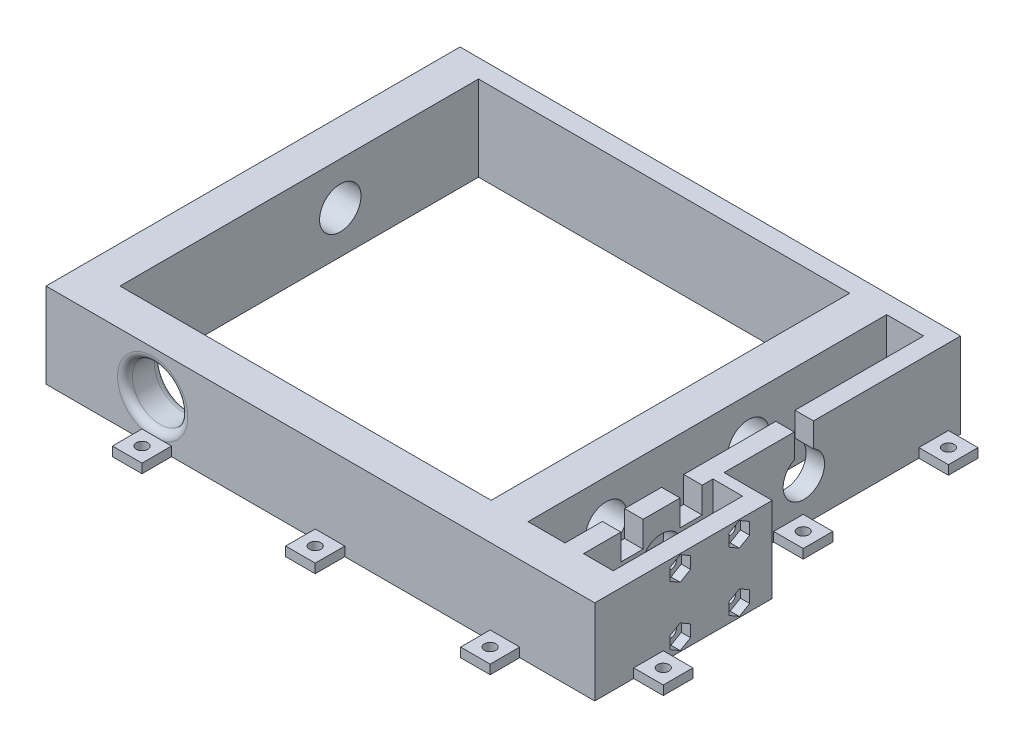
SolidWorks part; units mm, degrees
ref_plane "Front Plane" through (0, 0, 0) normal (0, 0, 1) x (1, 0, 0)
ref_plane "Top Plane" through (0, 0, 0) normal (0, 1, 0) x (1, 0, 0)
ref_plane "Right Plane" through (0, 0, 0) normal (1, 0, 0) x (0, 0, -1)
sketch "Sketch1" plane through (0, 0, 0) normal (0, 1, 0) x (1, 0, 0)
  line L0 (-50, -27.5) -> (-50, 27.5) construction
  line L1 (-40, -17.5) -> (40, -17.5) construction
  line L2 (-40, -17.5) -> (-40, 17.5) construction
  line L3 (-40, 17.5) -> (40, 17.5) construction
  line L4 (40, -17.5) -> (40, 17.5) construction
  line L5 (-40, -17.5) -> (40, 17.5) construction
  line L6 (-40, 17.5) -> (40, -17.5) construction
  line L7 (-50, 27.5) -> (50, 27.5) construction
  line L8 (50, -27.5) -> (50, 27.5) construction
  line L9 (-50, -27.5) -> (50, -27.5) construction
  line L10 (50, 0) -> (50.2, 0) construction
  line L11 (-50, 0) -> (-50.2, 0) construction
  line L12 (50.2, 0) -> (50.2, -27.5)
  line L13 (50.2, -27.5) -> (50.2, -47.5)
  line L14 (-50.2, 0) -> (-50.2, -27.5)
  line L15 (-50.2, -27.5) -> (-50.2, -47.5)
  line L16 (-50.2, -47.5) -> (50.2, -47.5)
  line L17 (50.2, 0) -> (50.2, 54.5)
  line L18 (-50.2, 0) -> (-50.2, 54.5)
  line L19 (-60.2, 0) -> (-60.2, 54.5)
  line L20 (-60.2, 0) -> (-60.2, -27.5)
  line L21 (-60.2, -27.5) -> (-60.2, -57.5)
  line L22 (-60.2, -57.5) -> (60.2, -57.5)
  line L23 (60.2, -27.5) -> (60.2, -57.5) construction
  line L24 (60.2, 0) -> (60.2, -27.5)
  line L25 (60.2, 0) -> (60.2, 54.5)
  line L26 (-50.2, 54.5) -> (-60.2, 54.5)
  line L27 (50.2, 54.5) -> (60.2, 54.5)
  line L28 (83.24, -47.5) -> (83.24, -9.5)
  line L29 (60.2, -57.5) -> (83.24, -57.5)
  line L31 (60.2, -47.5) -> (83.24, -47.5)
  line L32 (83.24, -57.5) -> (83.24, -47.5) construction
  line L33 (83.24, -57.5) -> (88.24, -57.5)
  line L34 (83.24, -57.5) -> (83.24, -9.5) construction
  line L35 (83.24, -9.5) -> (88.24, -9.5)
  line L36 (88.24, -57.5) -> (88.24, -9.5)
  line L37 (60.2, -47.5) -> (60.2, 54.5)
  line L39 (70.2, -47.5) -> (75.2, -47.5)
  line L40 (70.2, -47.5) -> (70.2, -9.5)
  line L41 (70.2, -9.5) -> (75.2, -9.5) construction
  line L42 (75.2, -47.5) -> (75.2, -9.5)
  line L43 (75.2, -9.5) -> (83.24, -9.5)
  line L44 (75.2, -9.5) -> (75.2, -12.5)
  line L45 (75.2, -12.5) -> (83.24, -12.5)
  line L46 (83.24, -9.5) -> (83.24, -12.5)
  line L47 (70.2, -9.5) -> (75.2, -9.5) construction
  line L48 (70.2, -9.5) -> (70.2, 54.5)
  line L49 (70.2, 54.5) -> (75.2, 54.5)
  line L50 (75.2, -9.5) -> (75.2, 54.5)
  line L51 (-50.2, 54.5) -> (50.2, 54.5)
  line L52 (-50.2, 54.5) -> (-50.2, 49.5)
  line L53 (-50.2, 49.5) -> (50.2, 49.5)
  line L54 (50.2, 54.5) -> (50.2, 49.5)
  line L55 (60.2, 54.5) -> (70.2, 54.5)
  line L56 (60.2, 54.5) -> (60.2, 49.5)
  line L57 (60.2, 49.5) -> (70.2, 49.5)
  line L58 (70.2, 54.5) -> (70.2, 49.5)
  point P0 (0, 0)
  point P10 (50, 0)
  point P11 (0, -27.5)
  point P12 (0, 27.5)
  point P13 (-50, 0)
  dimension "D1" = 80
  dimension "D2" = 35
  dimension "D4" = 0.2
  dimension "D5" = 20
  dimension "D7" = 8.04
  dimension "D8" = 5
  dimension "D9" = 10
  dimension "D10" = 5
  dimension "D11" = 38
  dimension "D12" = 3
  dimension "D13" = 22
  dimension "D14" = 5
  dimension "D3" = 10
  dimension "D6" = 10
extrude "Boss-Extrude1" add sketch "Sketch1" along normal mid plane 23 contours L31 L37 L24 L25 L27 L17 L12 L13 L16 L15 L14 L18 L26 L19 L20 L21 L22 L29 L33 L36 L35 L28 | L31 L42 L41 L40 | L42 L45 L28 L43 | L18 L53 L17 L51 | L37 L57 L48 L55 region at (52.0595, 0, -24.75) region at (0, 0, -52) region at (65.2, 0, -52) region at (72.7, 0, -3.5) region at (79.22, 0, 11)
sketch "Sketch2" plane through (60.2, 0, 0) normal (1, 0, 0) x (0, 0, -1)
  line L4 (-47.5, -11.5) -> (49.5, -11.5)
  line L5 (49.5, -11.5) -> (49.5, 11.5)
  line L6 (-47.5, -11.5) -> (49.5, -11.5)
  line L7 (49.5, 11.5) -> (-47.5, 11.5)
  line L12 (49.5, -11.5) -> (49.5, 11.5)
  line L14 (49.5, 11.5) -> (-47.5, 11.5)
  line L15 (-47.5, 11.5) -> (-47.5, -11.5)
  line L16 (-47.5, 11.5) -> (-47.5, -11.5)
  circle A0 centre (12.106, 0) radius 5.6
  circle A1 centre (12.106, 0) radius 34.1 construction
  circle A4 centre (-26.394, 0) radius 5.6
  circle A5 centre (-26.394, 0) radius 4.4 construction
  dimension "D2" = 11.2
  dimension "D3" = 68.2
  dimension "D5" = 8.8
  dimension "D4" = 38.5
  dimension "D1" = 0
extrude "Cut-Extrude1" cut sketch "Sketch2" against normal up to surface (120.4 mm away) contours A0 up to face at (-60.2, 0, 1.5)
sketch "Sketch3" plane through (60.2, 0, 0) normal (1, 0, 0) x (0, 0, -1)
  circle A0 centre (-26.394, 0) radius 5.6 construction
  circle A1 centre (-26.394, 0) radius 5.6
extrude "Cut-Extrude2" cut sketch "Sketch3" against normal up to next
sketch "Sketch8" plane through (70.2, 0, 0) normal (-1, 0, 0) x (0, 0, 1)
  circle A0 centre (26.394, 0) radius 5.6 construction
  circle A1 centre (26.394, 0) radius 5.6
extrude "Cut-Extrude5" cut sketch "Sketch8" against normal up to surface (5 mm away) up to face at (75.2, 0, 30)
sketch "Sketch10" plane through (83.24, 0, 0) normal (-1, 0, 0) x (0, 0, 1)
  line L1 (18.394, -8) -> (34.394, -8) construction
  line L2 (18.394, -8) -> (18.394, 8) construction
  line L3 (18.394, 8) -> (34.394, 8) construction
  line L4 (34.394, -8) -> (34.394, 8) construction
  line L5 (18.394, -8) -> (34.394, 8) construction
  line L6 (18.394, 8) -> (34.394, -8) construction
  circle A0 centre (26.394, 0) radius 5.6 construction
  circle A1 centre (26.394, 0) radius 5.6 construction
  circle A2 centre (18.394, 8) radius 1.8
  circle A3 centre (34.394, -8) radius 1.8
  circle A4 centre (18.394, -8) radius 1.8
  circle A5 centre (34.394, 8) radius 1.8
  dimension "D2" = 3.6
  dimension "D1" = 16
extrude "Boss-Extrude4" add sketch "Sketch10" along normal blind 1
sketch "Sketch11" plane through (82.24, 0, 0) normal (-1, 0, 0) x (0, 0, 1)
  circle A0 centre (18.394, 8) radius 1.5
  circle A1 centre (34.394, 8) radius 1.5
  circle A2 centre (34.394, -8) radius 1.5
  circle A3 centre (18.394, -8) radius 1.5
  dimension "D1" = 3
extrude "Cut-Extrude6" cut sketch "Sketch11" against normal up to surface (6 mm away) up to face at (88.24, 0, 33.5)
sketch "Sketch12" plane through (88.24, 0, 0) normal (1, 0, 0) x (0, 0, -1)
  line L1 (-31.594, 9.6166) -> (-34.394, 11.2332)
  line L2 (-34.394, 11.2332) -> (-37.194, 9.6166)
  line L3 (-37.194, 9.6166) -> (-37.194, 6.3834)
  line L4 (-57.5, -11.5) -> (-9.5, -11.5)
  line L5 (-9.5, -11.5) -> (-9.5, 11.5)
  line L6 (-9.5, 11.5) -> (-57.5, 11.5)
  line L7 (-57.5, 11.5) -> (-57.5, -11.5)
  line L8 (-57.5, -11.5) -> (-9.5, -11.5)
  line L10 (-9.5, 11.5) -> (-57.5, 11.5)
  line L12 (-37.194, 6.3834) -> (-34.394, 4.7668)
  line L13 (-34.394, 4.7668) -> (-31.594, 6.3834)
  line L14 (-31.594, 6.3834) -> (-31.594, 9.6166)
  line L15 (-18.394, 11.2332) -> (-21.194, 9.6166)
  line L16 (-21.194, 9.6166) -> (-21.194, 6.3834)
  line L17 (-21.194, 6.3834) -> (-18.394, 4.7668)
  line L18 (-18.394, 4.7668) -> (-15.594, 6.3834)
  line L19 (-15.594, 6.3834) -> (-15.594, 9.6166)
  line L20 (-15.594, 9.6166) -> (-18.394, 11.2332)
  line L21 (-31.594, -6.3834) -> (-34.394, -4.7668)
  line L22 (-34.394, -4.7668) -> (-37.194, -6.3834)
  line L23 (-37.194, -6.3834) -> (-37.194, -9.6166)
  line L24 (-37.194, -9.6166) -> (-34.394, -11.2332)
  line L25 (-34.394, -11.2332) -> (-31.594, -9.6166)
  line L26 (-31.594, -9.6166) -> (-31.594, -6.3834)
  line L27 (-15.594, -6.3834) -> (-18.394, -4.7668)
  line L28 (-18.394, -4.7668) -> (-21.194, -6.3834)
  line L29 (-21.194, -6.3834) -> (-21.194, -9.6166)
  line L30 (-21.194, -9.6166) -> (-18.394, -11.2332)
  line L31 (-18.394, -11.2332) -> (-15.594, -9.6166)
  line L32 (-15.594, -9.6166) -> (-15.594, -6.3834)
  line L36 (-9.5, -11.5) -> (-9.5, 11.5)
  line L38 (-57.5, 11.5) -> (-57.5, -11.5)
  circle A0 centre (-34.394, 8) radius 2.8 construction
  circle A1 centre (-18.394, 8) radius 2.8 construction
  circle A2 centre (-34.394, -8) radius 2.8 construction
  circle A3 centre (-18.394, -8) radius 2.8 construction
  circle M5 centre (-18.394, -8) radius 1.5
  circle M6 centre (-34.394, -8) radius 1.5
  circle M7 centre (-34.394, 8) radius 1.5
  circle M8 centre (-18.394, 8) radius 1.5
  line M11 (-9.5, 11.5) -> (-57.5, 11.5)
  dimension "D2" = 5.6
  dimension "D1" = 0
extrude "Cut-Extrude7" cut sketch "Sketch12" against normal blind 2.5 contours L13 L14 L1 L2 L3 L12 M11 M7 | L19 L20 L10 L15 L16 L17 L18 M8 | L31 L32 L27 L28 L29 L30 L8 M5 | L25 L26 L21 L22 L23 L24 L8 M6 region at (88.24, 8, 31.6795) region at (88.24, 10.3508, 17.0368) region at (88.24, -8, 31.6795) region at (88.24, -8, 15.6795)
sketch "Sketch13" plane through (75.2, 0, 0) normal (1, 0, 0) x (0, 0, -1)
  line L0 (-57.5, 11.5) -> (-9.5, 11.5) construction
  line L1 (-37.394, 4.5) -> (-31.394, 4.5)
  line L2 (-37.394, 4.5) -> (-37.394, 11.5)
  line L3 (-37.394, 11.5) -> (-31.394, 11.5)
  line L4 (-31.394, 4.5) -> (-31.394, 11.5)
  line L5 (-37.394, 4.5) -> (-31.394, 11.5) construction
  line L6 (-37.394, 11.5) -> (-31.394, 4.5) construction
  line L7 (-21.394, 4.5) -> (-15.394, 4.5)
  line L8 (-21.394, 4.5) -> (-21.394, 11.5)
  line L9 (-21.394, 11.5) -> (-15.394, 11.5)
  line L10 (-15.394, 4.5) -> (-15.394, 11.5)
  line L11 (-21.394, 4.5) -> (-15.394, 11.5) construction
  line L12 (-21.394, 11.5) -> (-15.394, 4.5) construction
  line L13 (-21.394, -11.5) -> (-15.394, -11.5)
  line L14 (-21.394, -11.5) -> (-21.394, -4.5)
  line L15 (-21.394, -4.5) -> (-15.394, -4.5)
  line L16 (-15.394, -11.5) -> (-15.394, -4.5)
  line L17 (-21.394, -11.5) -> (-15.394, -4.5) construction
  line L18 (-21.394, -4.5) -> (-15.394, -11.5) construction
  line L19 (-37.394, -11.5) -> (-31.394, -11.5)
  line L20 (-37.394, -11.5) -> (-37.394, -4.5)
  line L21 (-37.394, -4.5) -> (-31.394, -4.5)
  line L22 (-31.394, -11.5) -> (-31.394, -4.5)
  line L23 (-37.394, -11.5) -> (-31.394, -4.5) construction
  line L24 (-37.394, -4.5) -> (-31.394, -11.5) construction
  line L25 (-57.5, -11.5) -> (-9.5, -11.5) construction
  circle A0 centre (-34.394, -8) radius 1.5 construction
  circle A1 centre (-18.394, -8) radius 1.5 construction
  circle A2 centre (-18.394, 8) radius 1.5 construction
  circle A3 centre (-34.394, 8) radius 1.5 construction
  circle A4 centre (-34.394, -8) radius 1.5 construction
  circle A5 centre (-18.394, -8) radius 1.5 construction
  circle A6 centre (-18.394, 8) radius 1.5 construction
  circle A7 centre (-34.394, 8) radius 1.5 construction
  point P23 (-18.394, 8)
  point P28 (-18.394, -8)
  point P33 (-34.394, -8)
  dimension "D1" = 6
extrude "Cut-Extrude9" cut sketch "Sketch13" against normal up to surface (5 mm away) up to face at (70.2, 0, 31.994)
sketch "Sketch14" plane through (70.2, 0, 0) normal (-1, 0, 0) x (0, 0, 1)
  line L0 (15.394, 11.5) -> (-49.5, 11.5) construction
  line L1 (-14.706, 4.9598) -> (-9.506, 4.9598)
  line L2 (-14.706, 4.9598) -> (-14.706, 11.5)
  line L3 (-14.706, 11.5) -> (-9.506, 11.5)
  line L4 (-9.506, 4.9598) -> (-9.506, 11.5)
  circle A0 centre (-12.106, 0) radius 5.6 construction
  circle A1 centre (-12.106, 0) radius 5.6
  line M13 (15.394, 11.5) -> (-49.5, 11.5)
  dimension "D1" = 5.2
extrude "Cut-Extrude10" cut sketch "Sketch14" against normal up to next contours L1 A1 | A1 L4 L2 M13 | L1 A1 region at (70.2, 5.2172, -12.106) region at (70.2, 8.4429, -12.106) region at (70.2, -0.1217, -12.106)
sketch "Sketch15" plane through (0, 0, 57.5) normal (0, 0, 1) x (1, 0, 0)
  line L5 (-60.2, -11.5) -> (88.24, -11.5) construction
  line L6 (-34.3437, -11.5) -> (-28.3437, -11.5)
  circle A0 centre (-31.3437, 0) radius 7.5
  dimension "D3" = 15
extrude "Cut-Extrude11" cut sketch "Sketch15" against normal up to surface (10 mm away) contours A0 region at (-31.3437, 0, 57.5) up to face at (0, 0, 47.5)
fillet "Fillet1" radius 2 2 edges at (-38.8437, 0, 47.5) (-23.8437, 0, 57.5)
sketch "Sketch16" plane through (0, -11.5, 0) normal (0, -1, 0) x (1, 0, 0)
  line L0 (-60.2, 57.5) -> (-60.2, -54.5) construction
  line L1 (-60.2, -54.5) -> (75.2, -54.5) construction
  line L2 (75.2, 9.5) -> (75.2, -54.5) construction
  line L3 (88.24, 57.5) -> (88.24, 9.5) construction
  line L4 (-60.2, 57.5) -> (88.24, 57.5) construction
  line L6 (-26.235, 57.5) -> (-34.235, 57.5)
  line L7 (-26.235, 57.5) -> (-26.235, 65.5)
  line L8 (-26.235, 65.5) -> (-34.235, 65.5)
  line L9 (-34.235, 57.5) -> (-34.235, 65.5)
  line L10 (-60.2, 44.1008) -> (-68.2, 44.1008)
  line L11 (-60.2, 44.1008) -> (-60.2, 36.1008)
  line L12 (-60.2, 36.1008) -> (-68.2, 36.1008)
  line L13 (-68.2, 44.1008) -> (-68.2, 36.1008)
  line L14 (-60.2, -36.5827) -> (-68.2, -36.5827)
  line L15 (-60.2, -36.5827) -> (-60.2, -44.5827)
  line L16 (-60.2, -44.5827) -> (-68.2, -44.5827)
  line L17 (-68.2, -36.5827) -> (-68.2, -44.5827)
  line L18 (-36.4203, -54.5) -> (-28.4203, -54.5)
  line L19 (-36.4203, -54.5) -> (-36.4203, -62.5)
  line L20 (-36.4203, -62.5) -> (-28.4203, -62.5)
  line L21 (-28.4203, -54.5) -> (-28.4203, -62.5)
  line L22 (-5.3881, -54.5) -> (2.6119, -54.5)
  line L23 (-5.3881, -54.5) -> (-5.3881, -62.5)
  line L24 (-5.3881, -62.5) -> (2.6119, -62.5)
  line L25 (2.6119, -54.5) -> (2.6119, -62.5)
  line L26 (46.8273, -54.5) -> (54.8273, -54.5)
  line L27 (46.8273, -54.5) -> (46.8273, -62.5)
  line L28 (46.8273, -62.5) -> (54.8273, -62.5)
  line L29 (54.8273, -54.5) -> (54.8273, -62.5)
  line L30 (75.2, -51.208) -> (83.2, -51.208)
  line L31 (75.2, -51.208) -> (75.2, -43.208)
  line L32 (75.2, -43.208) -> (83.2, -43.208)
  line L33 (83.2, -51.208) -> (83.2, -43.208)
  line L34 (75.2, -11.9306) -> (83.2, -11.9306)
  line L35 (75.2, -11.9306) -> (75.2, -3.9306)
  line L36 (75.2, -3.9306) -> (83.2, -3.9306)
  line L37 (83.2, -11.9306) -> (83.2, -3.9306)
  line L38 (88.24, 38.9621) -> (96.24, 38.9621)
  line L39 (88.24, 38.9621) -> (88.24, 46.9621)
  line L40 (88.24, 46.9621) -> (96.24, 46.9621)
  line L41 (96.24, 38.9621) -> (96.24, 46.9621)
  line L42 (67.9476, 57.5) -> (59.9476, 57.5)
  line L43 (67.9476, 57.5) -> (67.9476, 65.5)
  line L44 (67.9476, 65.5) -> (59.9476, 65.5)
  line L45 (59.9476, 57.5) -> (59.9476, 65.5)
  line L46 (20.6236, 57.5) -> (12.6236, 57.5)
  line L47 (20.6236, 57.5) -> (20.6236, 65.5)
  line L48 (20.6236, 65.5) -> (12.6236, 65.5)
  line L49 (12.6236, 57.5) -> (12.6236, 65.5)
  circle A0 centre (-30.235, 61.5) radius 1.55
  circle A1 centre (16.6236, 61.5) radius 1.55
  circle A2 centre (63.9476, 61.5) radius 1.55
  circle A3 centre (92.24, 42.9621) radius 1.55
  circle A4 centre (79.2, -7.9306) radius 1.55
  circle A5 centre (79.2, -47.208) radius 1.55
  circle A6 centre (50.8273, -58.5) radius 1.55
  circle A7 centre (-1.3881, -58.5) radius 1.55
  circle A8 centre (-32.4203, -58.5) radius 1.55
  circle A9 centre (-64.2, -40.5827) radius 1.55
  circle A10 centre (-64.2, 40.1008) radius 1.55
  point P0 (-60.2, 41.1522)
  point P1 (-60.2, -39.1219)
  point P4 (-32.9592, -54.5)
  point P5 (1.1977, -54.5)
  point P8 (48.3924, -54.5)
  point P9 (75.2, -43.1087)
  point P10 (75.2, -10.4603)
  point P13 (88.24, 41.1522)
  point P14 (65.848, 57.5)
  point P17 (18.761, 57.5)
  point P20 (-30.5887, 57.5)
  point P65 (-30.235, 65.5)
  point P66 (-30.235, 61.5)
  point P67 (16.6236, 61.5)
  point P68 (63.9476, 61.5)
  point P69 (-64.2, 40.1008)
  point P70 (-64.2, -40.5827)
  point P71 (-32.4203, -58.5)
  point P72 (-1.3881, -58.5)
  point P73 (50.8273, -58.5)
  point P74 (79.2, -47.208)
  point P75 (79.2, -7.9306)
  point P76 (92.24, 42.9621)
  dimension "D2" = 3.1
  dimension "D1" = 8
extrude "Boss-Extrude5" add sketch "Sketch16" against normal blind 2.5 separate body
equation "\"a\"= 1"
equation "\"b\"= 1"
equation "\"c\"= 1"
equation "\"d\"= 1"
equation "\"e\"= 1"
equation "\"x\"= 1"
equation "\"y\"= 1"
equation "\"z\"= 1"
